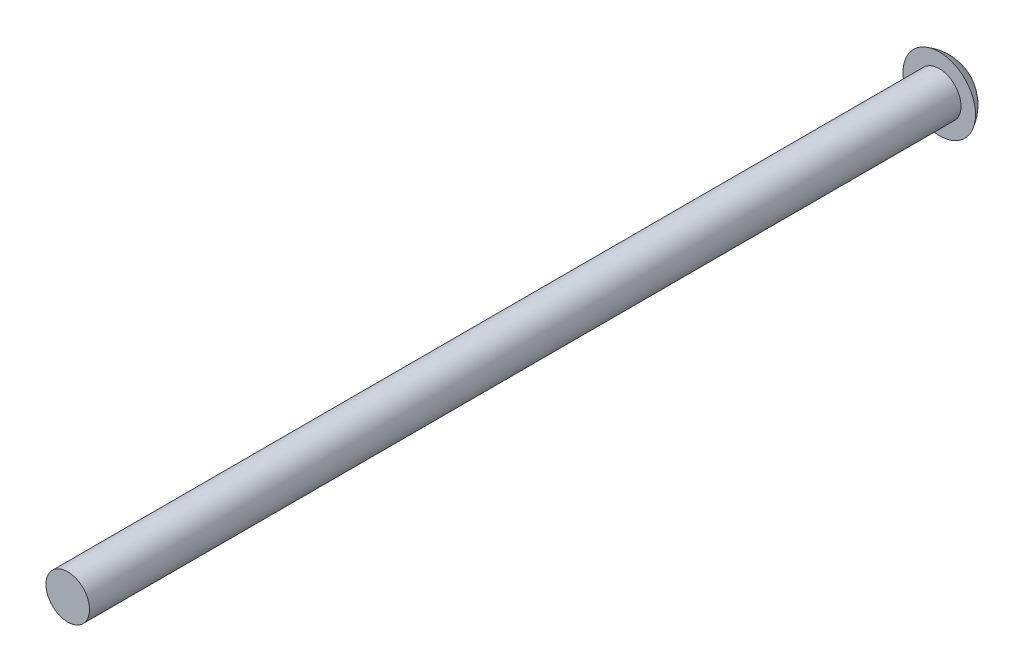
SolidWorks part; units mm, degrees
material "镀铬不锈钢"
ref_plane "前视基准面" through (0, 0, 0) normal (0, 0, 1) x (1, 0, 0)
ref_plane "上视基准面" through (0, 0, 0) normal (0, 1, 0) x (1, 0, 0)
ref_plane "右视基准面" through (0, 0, 0) normal (1, 0, 0) x (0, 0, -1)
sketch "草图1" plane through (0, 0, 0) normal (0, 0, 1) x (1, 0, 0)
  circle A0 centre (0, 0) radius 3
  dimension "D1" = 6
extrude "凸台-拉伸1" add sketch "草图1" along normal blind 120
sketch "草图2" plane through (0, 0, 0) normal (0, 1, 0) x (1, 0, 0)
  line L0 (0, 0) -> (5, 0)
  line L1 (0, 0) -> (0, 3)
  arc A0 (0, 3) -> (5, 0) centre (0, -2.6667) cw
  dimension "D1" = 5
  dimension "D2" = 3
revolve "旋转1" add sketch "草图2" angle 360 about L1
